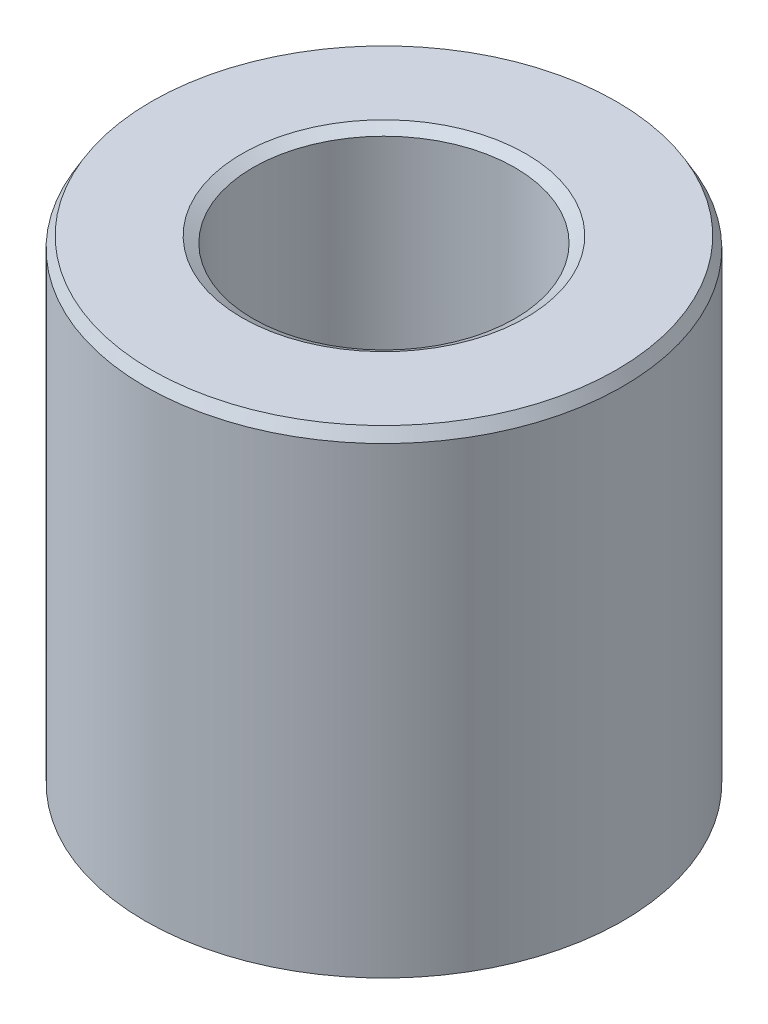
SolidWorks part; units mm, degrees
ref_plane "Front Plane" through (0, 0, 0) normal (0, 0, 1) x (1, 0, 0)
ref_plane "Top Plane" through (0, 0, 0) normal (0, 1, 0) x (1, 0, 0)
ref_plane "Right Plane" through (0, 0, 0) normal (1, 0, 0) x (0, 0, -1)
sketch "Sketch1" plane through (0, 0, 0) normal (0, 1, 0) x (1, 0, 0)
  circle A0 centre (0, 0) radius 30
  dimension "SLEEVE_OD" = 60
extrude "Boss-Extrude1" add sketch "Sketch1" along normal blind 60.3175
sketch "Sketch2" plane through (0, 0, 0) normal (0, 1, 0) x (1, 0, 0)
  circle A0 centre (0, 0) radius 16.4404
  dimension "BORE_D" = 32.8808
extrude "Cut-Extrude1" cut sketch "Sketch2" along normal through all
chamfer "Chamfer1" distance 1.3915 angle 30 4 edges at (0, 60.3175, 16.4404) (0, 0, 16.4404) (0, 0, 30) (0, 60.3175, 30) first distance on face at (0, 60.3175, 16.4404) first distance on face at (0, 0, 16.4404) first distance on face at (0, 60.3175, 30)
